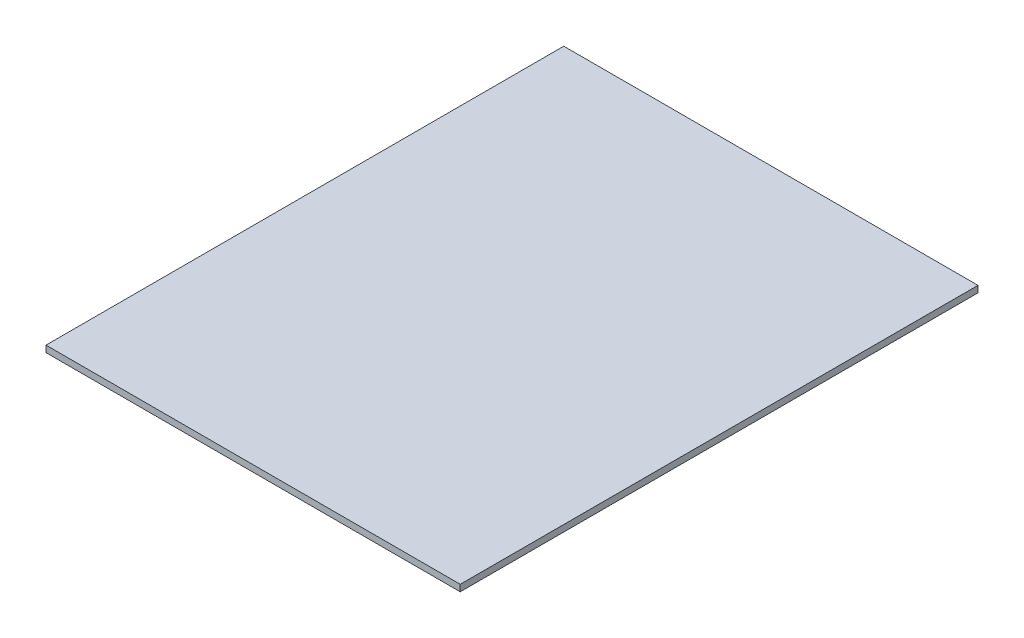
SolidWorks part; units mm, degrees
ref_plane "Front" through (0, 0, 0) normal (0, 0, 1) x (1, 0, 0)
ref_plane "Top" through (0, 0, 0) normal (0, 1, 0) x (1, 0, 0)
ref_plane "Right" through (0, 0, 0) normal (1, 0, 0) x (0, 0, -1)
sketch "Sketch1" plane through (0, 0, 0) normal (0, 1, 0) x (1, 0, 0)
  line L1 (-50.8, -63.5) -> (50.8, -63.5)
  line L2 (-50.8, -63.5) -> (-50.8, 63.5)
  line L3 (-50.8, 63.5) -> (50.8, 63.5)
  line L4 (50.8, -63.5) -> (50.8, 63.5)
  line L5 (-50.8, -63.5) -> (50.8, 63.5) construction
  line L6 (-50.8, 63.5) -> (50.8, -63.5) construction
  point P0 (0, 0)
  dimension "D1" = 127
  dimension "D2" = 101.6
extrude "Boss-Extrude1" add sketch "Sketch1" along normal blind 1.6
